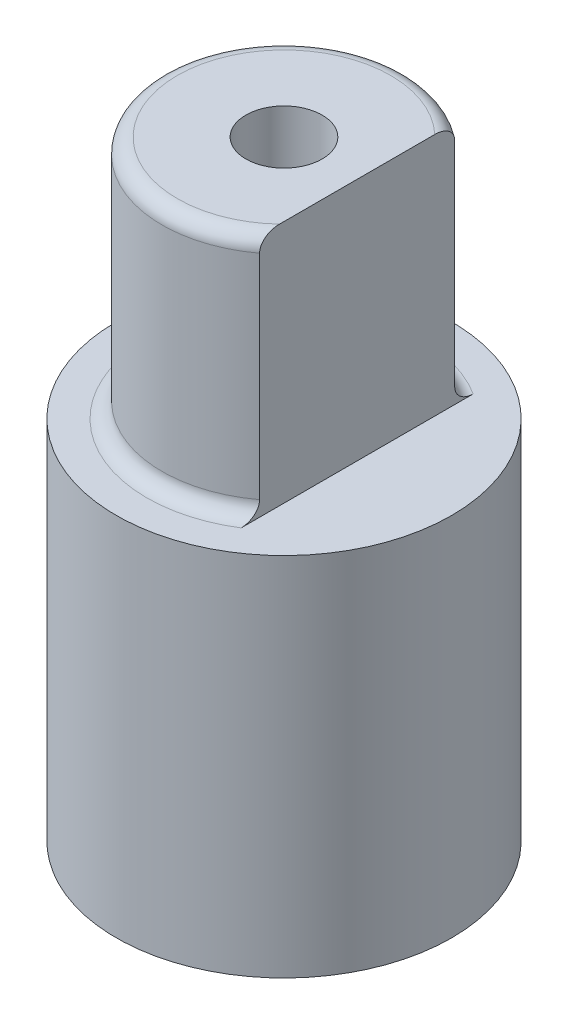
SolidWorks part; units mm, degrees
material "PE(聚乙烯)"
ref_plane "前视" through (0, 0, 0) normal (0, 0, 1) x (1, 0, 0)
ref_plane "上视" through (0, 0, 0) normal (0, 1, 0) x (1, 0, 0)
ref_plane "右视" through (0, 0, 0) normal (1, 0, 0) x (0, 0, -1)
sketch "草图1" plane through (0, 0, 0) normal (0, 0, 1) x (1, 0, 0)
  line L0 (0, 0) -> (0, -10)
  line L1 (0, 0) -> (4, 0)
  line L2 (4, 0) -> (4, -8)
  line L3 (4, -8) -> (5.5, -8)
  line L4 (5.5, -8) -> (5.5, -20)
  line L5 (5.5, -20) -> (0.5, -20)
  line L6 (0.5, -20) -> (0.5, -10)
  line L7 (0.5, -10) -> (0, -10)
  line L8 (0, 0) -> (0, -17.2441) construction
  dimension "D1" = 8
  dimension "D2" = 8
  dimension "D3" = 12
  dimension "D4" = 11
  dimension "D5" = 1
  dimension "D6" = 10
revolve "旋转1" add sketch "草图1" angle 360 about L8
hole_wizard "M3 螺纹孔1" positions "草图3" profile "草图2" tap size "M3" standard "GB"
sketch "草图3" plane through (0, 0, 0) normal (0, 1, 0) x (1, 0, 0)
  point P0 (0, 0)
sketch "草图2" plane through (0, 0, 0) normal (1, 0, 0) x (0, 0, 1)
  line L0 (0, 0) -> (0, 7.999)
  line L1 (0, 7.999) -> (1.25, 7.2479)
  line L2 (1.25, 7.2479) -> (1.25, 0)
  line L5 (1.25, 0) -> (0, 0)
  line L10 (0, 7.999) -> (-1.25, 7.2479) construction
  line L11 (0, -6.35) -> (0, 107.95) construction
  dimension "螺纹孔钻头直径" = 2.5
  dimension "螺纹孔钻头深度" = 7.999
  dimension "导头角度" = 118
cosmetic thread "孔螺蚊线3" parameters "D1"=8, "D2"=3
ref_plane "基准面1" through (-5.5, 0, 0) normal (-1, 0, 0) x (0, 0, 1)
sketch "草图7" plane through (0, -20, 0) normal (0, -1, 0) x (1, 0, 0)
  line L0 (-1, 1.118) -> (-1, -1.118)
  arc A0 (-1, -1.118) -> (-1, 1.118) centre (0, 0) ccw
  dimension "D1" = 1.5
  dimension "D2" = 1
extrude "切除-拉伸1" cut sketch "草图7" against normal blind 10
ref_plane "基准面2" through (2.4, 0, 0) normal (1, 0, 0) x (0, 0, -1)
sketch "草图8" plane through (2.4, 0, 0) normal (1, 0, 0) x (0, 0, -1)
  line L0 (5.5, -8) -> (-5.5, -8) construction
  line L1 (-4.6356, -8) -> (6.8468, -8)
  line L2 (-4.6356, -8) -> (-4.6356, 0.7356)
  line L3 (-4.6356, 0.7356) -> (6.8468, 0.7356)
  line L4 (6.8468, -8) -> (6.8468, 0.7356)
extrude "切除-拉伸2" cut sketch "草图8" along normal through all
fillet "圆角1" radius 1 2 edges at (-1, -15, -1.118) (-1, -15, 1.118)
hole_wizard "M3 螺纹孔2" positions "草图6" profile "草图5" tap size "M3" standard "GB"
sketch "草图6" plane through (-5.5, 0, 0) normal (-1, 0, 0) x (0, 0, 1)
  line L0 (-5.5, -20) -> (5.5, -20) construction
  line L1 (0, 0) -> (0, -20) construction
  point P0 (0, -17)
  dimension "D1" = 3
sketch "草图5" plane through (-5.5, -17, 0) normal (0, 1, 0) x (0, 0, 1)
  line L0 (0, 0) -> (0, 6)
  line L1 (0, 6) -> (1.25, 5.2489)
  line L2 (1.25, 5.2489) -> (1.25, 0)
  line L5 (1.25, 0) -> (0, 0)
  line L10 (0, 6) -> (-1.25, 5.2489) construction
  line L11 (0, -6.35) -> (0, 107.95) construction
  dimension "螺纹孔钻头直径" = 2.5
  dimension "螺纹孔钻头深度" = 6
  dimension "导头角度" = 118
cosmetic thread "孔螺蚊线4" parameters "D1"=6, "D2"=3
fillet "圆角2" radius 0.5 2 edges at (-4, -8, 0) (-4, 0, 0)
